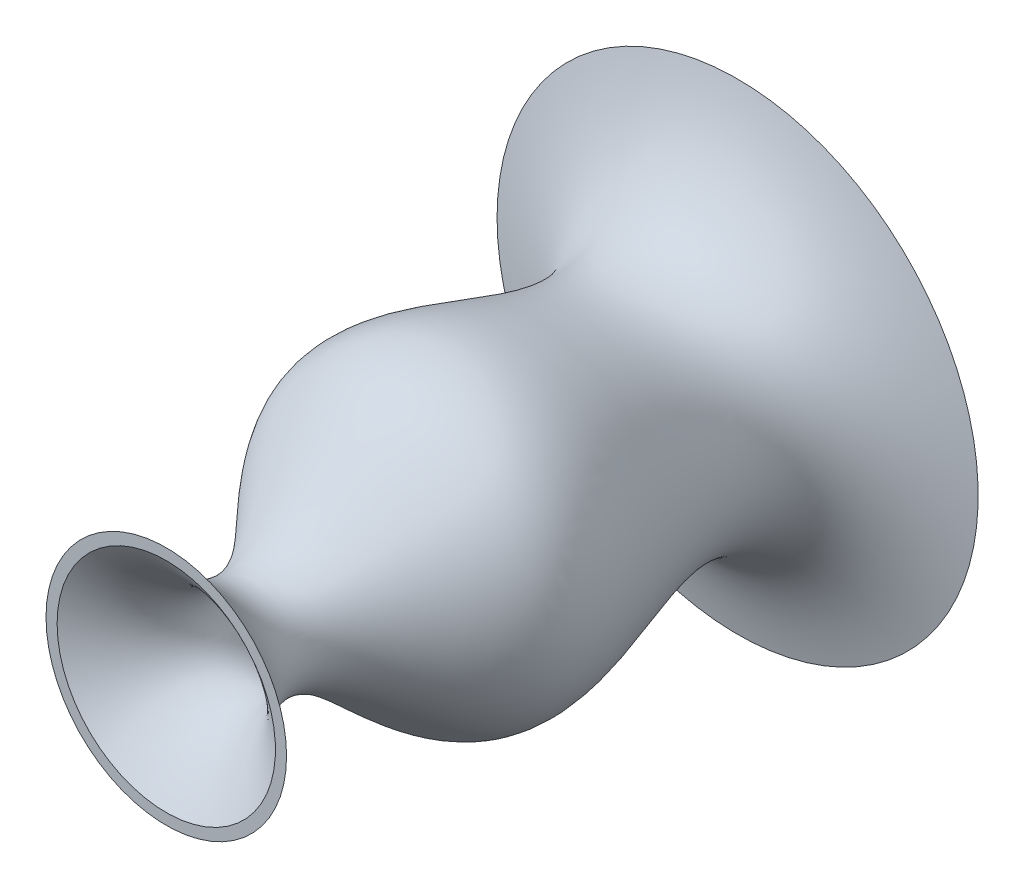
SolidWorks part; units mm, degrees
ref_plane "Front Plane" through (0, 0, 0) normal (1, 0, 0) x (0, 1, 0)
ref_plane "Top Plane" through (0, 0, 0) normal (0, 0, 1) x (0, 1, 0)
ref_plane "Right Plane" through (0, 0, 0) normal (0, 1, 0) x (-1, 0, 0)
sketch "Sketch1" plane through (0, 0, 0) normal (1, 0, 0) x (0, 1, 0)
  line L0 (0, 0) -> (0, 241.3)
  line L1 (0, 241.3) -> (50.8, 241.3)
  line L2 (0, 0) -> (101.6, 0)
  spline S0 degree 3 poles (50.8, 241.3) (-17.1723, 198.7081) (140.9896, 144.4488) (-0.615, 24.6496) (101.6, 0) knots 0 0 0 0 0.431375 1 1 1 1
  dimension "D1" = 241.3
  dimension "D2" = 25.4
  dimension "D3" = 63.5
  dimension "D4" = 50.8
  dimension "D5" = 50.8
  dimension "D6" = 101.6
  dimension "D7" = 50.8
  dimension "D8" = 101.6
  dimension "D9" = 177.8
revolve "Revolve1" add sketch "Sketch1" angle 360 about L0 region at (0, 27.6371, 105.2243)
shell "Shell1" thickness 2.54 removed face at (-50.8, 0, 241.3)
